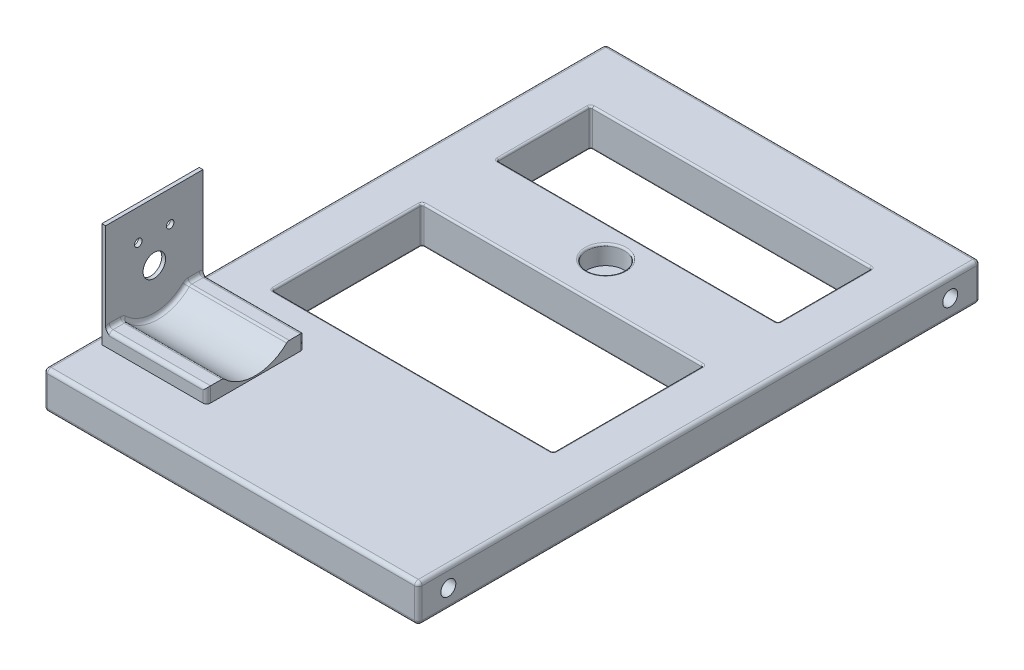
SolidWorks part; units mm, degrees
material "ABS"
ref_plane "Front Plane" through (0, 0, 0) normal (0, 0, 1) x (1, 0, 0)
ref_plane "Top Plane" through (0, 0, 0) normal (0, 1, 0) x (1, 0, 0)
ref_plane "Right Plane" through (0, 0, 0) normal (1, 0, 0) x (0, 0, -1)
sketch "Sketch2" plane through (0, 0, 0) normal (0, 1, 0) x (1, 0, 0)
  line L0 (0, 0) -> (0, 150)
  line L1 (0, 150) -> (100, 150)
  line L2 (100, 150) -> (100, 0)
  line L3 (100, 0) -> (0, 0)
  dimension "D1" = 100
  dimension "D2" = 150
extrude "Boss-Extrude1" add sketch "Sketch2" along normal blind 10
sketch "Sketch3" plane through (0, 10, 0) normal (0, 1, 0) x (1, 0, 0)
  line L0 (50, 150) -> (50, 100) construction
  line L1 (100, 150) -> (0, 150) construction
  circle A0 centre (50, 100) radius 5
  dimension "D2" = 10
  dimension "D1" = 50
extrude "MountHole" cut sketch "Sketch3" against normal blind 5
sketch "Sketch4" plane through (0, 0, 0) normal (-1, 0, 0) x (0, 0, 1)
  line L0 (-8, 10) -> (-8, 0) construction
  line L1 (-150, 10) -> (0, 10) construction
  line L2 (-150, 0) -> (0, 0) construction
  line L3 (0, 10) -> (0, 0) construction
  circle A0 centre (-8, 5) radius 2
  dimension "D2" = 4
  dimension "D1" = 8
extrude "Cut-Extrude2" cut sketch "Sketch4" against normal through all
sketch "Sketch5" plane through (0, 0, 0) normal (-1, 0, 0) x (0, 0, 1)
  line L0 (-142, 10) -> (-142, 0) construction
  line L1 (-150, 10) -> (0, 10) construction
  line L2 (-150, 0) -> (0, 0) construction
  line L3 (-150, 10) -> (-150, 0) construction
  circle A0 centre (-142, 5) radius 2
  dimension "D2" = 4
  dimension "D1" = 8
extrude "Cut-Extrude3" cut sketch "Sketch5" against normal through all
fillet "Fillet1" [suppressed] radius 2
sketch "Sketch7" plane through (0, 10, 0) normal (0, 1, 0) x (1, 0, 0)
  line L0 (11, 0) -> (11, 26) construction
  line L1 (0, 0) -> (100, 0) construction
  line L2 (0, 150) -> (0, 0) construction
  line L3 (11, 26) -> (47.1706, 26) construction
  line L9 (11, 26) -> (-5.1328, 26) construction
  line L15 (2.5, 39) -> (2.5, 13)
  line L16 (2.5, 39) -> (30.5, 39)
  line L17 (30.5, 39) -> (30.5, 13)
  line L18 (30.5, 13) -> (2.5, 13)
  point P10 (2.5, 26)
  dimension "D1" = 26
  dimension "D2" = 11
  dimension "D3" = 26
  dimension "D4" = 28
  dimension "D5" = 8.5
extrude "Boss-Extrude2" add sketch "Sketch7" along normal blind 4
sketch "Sketch10" plane through (0, 14, 0) normal (0, 1, 0) x (1, 0, 0)
  line L0 (2.5, 39) -> (2.5, 13)
  line L1 (2.5, 13) -> (3.5, 13)
  line L2 (2.5, 13) -> (30.5, 13) construction
  line L3 (3.5, 13) -> (3.5, 39)
  line L4 (30.5, 39) -> (2.5, 39) construction
  line L5 (3.5, 39) -> (2.5, 39)
  dimension "D1" = 1
extrude "Boss-Extrude3" add sketch "Sketch10" along normal blind 24
sketch "Sketch11" plane through (30.5, 0, 0) normal (1, 0, 0) x (0, 0, -1)
  line L0 (13, 14) -> (39, 14) construction
  line L1 (13, 14) -> (17.3857, 14)
  line L2 (34.6143, 14) -> (39, 14)
  arc A0 (17.3857, 14) -> (34.6143, 14) centre (26, 22.3543) ccw
  dimension "D1" = 12
extrude "Cut-Extrude5" cut sketch "Sketch11" against normal blind 27 and the other way through all
sketch "Sketch13" plane through (2.5, 0, 0) normal (-1, 0, 0) x (0, 0, 1)
  line L0 (-26, 10) -> (-26, 22.354) construction
  line L1 (-39, 10) -> (-13, 10) construction
  line L2 (-26, 22.354) -> (-21.75, 29.7152) construction
  line L3 (-26, 22.354) -> (-6.4369, 22.354) construction
  line L4 (-26, 22.354) -> (-30.25, 29.7152) construction
  circle A0 centre (-26, 22.354) radius 3
  circle A1 centre (-21.75, 29.7152) radius 1
  circle A2 centre (-30.25, 29.7152) radius 1
  dimension "D2" = 6
  dimension "D5" = 2
  dimension "D8" = 2
  dimension "D1" = 12.354
  dimension "D3" = 60
  dimension "D4" = 8.5
  dimension "D6" = 120
  dimension "D7" = 8.5
extrude "Cut-Extrude6" cut sketch "Sketch13" against normal up to surface (1 mm away) up to face at (3.5, 21.3924, -26)
fillet "Fillet2" radius 1 6 edges at (30.5, 12, -39) (17, 14, -39) (17, 14, -34.6143) (17, 14, -17.3857) (30.5, 12, -13) (17, 14, -13)
fillet "Fillet3" radius 1 7 edges at (3.5, 13.7071, -38.7071) (3.5, 14, -36.5138) (3.5, 13.9272, -34.6531) (3.5, 13.7071, -13.2929) (3.5, 14, -15.4862) (3.5, 13.9272, -17.3469) (3.5, 10.3543, -26)
fillet "Fillet4" radius 1 12 edges at (50, 0, -150) (100, 5, -150) (50, 10, -150) (0, 5, -150) (0, 0, -75) (0, 10, -75) (100, 0, -75) (100, 10, -75) (100, 5, 0) (50, 0, 0) (50, 10, 0) (0, 5, 0)
sketch "Sketch14" plane through (0, 10, 0) normal (0, 1, 0) x (1, 0, 0)
  line L0 (50, 0) -> (50, 149) construction
  line L1 (99, 0) -> (1, 0) construction
  line L2 (99, 149) -> (1, 149) construction
  line L4 (12.5, 133.5) -> (87.5, 133.5)
  line L5 (12.5, 133.5) -> (12.5, 108.5)
  line L6 (12.5, 108.5) -> (87.5, 108.5)
  line L7 (87.5, 133.5) -> (87.5, 108.5)
  line L8 (12.5, 133.5) -> (87.5, 108.5) construction
  line L9 (12.5, 108.5) -> (87.5, 133.5) construction
  line L10 (12.5, 88.5) -> (87.5, 88.5)
  line L11 (12.5, 88.5) -> (12.5, 48.5)
  line L12 (12.5, 48.5) -> (87.5, 48.5)
  line L13 (87.5, 88.5) -> (87.5, 48.5)
  line L14 (12.5, 88.5) -> (87.5, 48.5) construction
  line L15 (12.5, 48.5) -> (87.5, 88.5) construction
  point P6 (50, 121)
  point P11 (50, 68.5)
  dimension "D1" = 75
  dimension "D2" = 25
  dimension "D3" = 28
  dimension "D4" = 75
  dimension "D5" = 40
  dimension "D6" = 40
extrude "Cut-Extrude7" cut sketch "Sketch14" against normal through all
fillet "Fillet5" radius 0.5 25 edges at (12.5, 0, -121) (87.5, 0, -68.5) (12.5, 0, -68.5) (12.5, 5, -108.5) (87.5, 5, -108.5) (50, 0, -108.5) (87.5, 0, -121) (87.5, 5, -133.5) (12.5, 5, -133.5) (50, 0, -133.5) (87.5, 10, -121) (50, 10, -133.5) (12.5, 10, -121) (50, 10, -108.5) (50, 10, -95) (12.5, 5, -48.5) (87.5, 5, -48.5) (50, 0, -48.5) (87.5, 5, -88.5) (50, 0, -88.5) (12.5, 5, -88.5) (87.5, 10, -68.5) (50, 10, -48.5) (12.5, 10, -68.5) (50, 10, -88.5)
